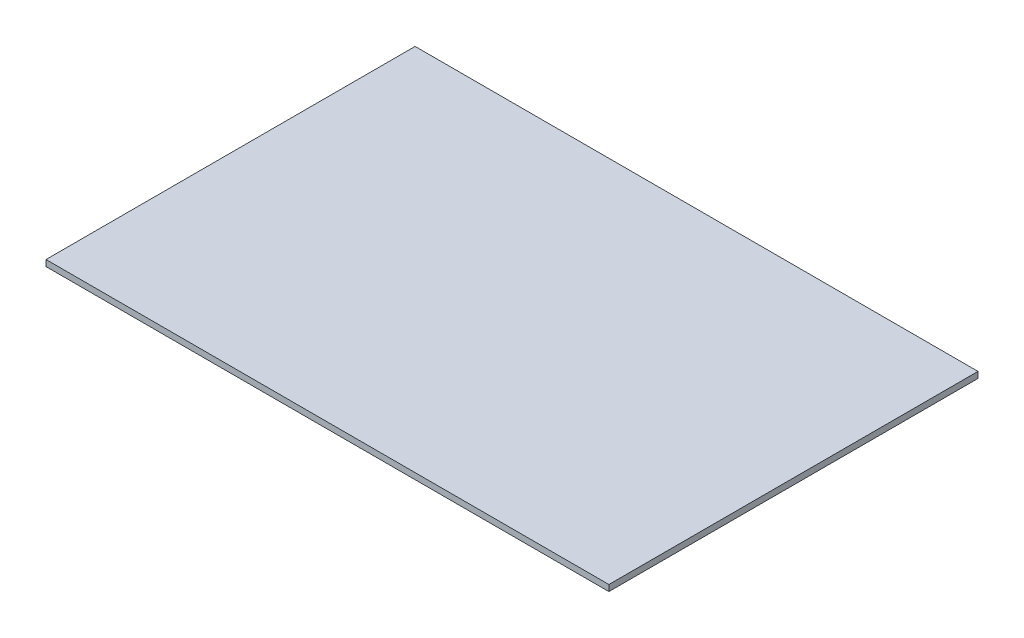
SolidWorks part; units mm, degrees
ref_plane "Front Plane" through (0, 0, 0) normal (0, 0, 1) x (1, 0, 0)
ref_plane "Top Plane" through (0, 0, 0) normal (0, 1, 0) x (1, 0, 0)
ref_plane "Right Plane" through (0, 0, 0) normal (1, 0, 0) x (0, 0, -1)
sketch "Sketch1" plane through (0, 0, 0) normal (0, 1, 0) x (1, 0, 0)
  line L1 (0, 0) -> (914.4, 0)
  line L2 (0, 0) -> (0, 609.6)
  line L3 (0, 609.6) -> (914.4, 609.6)
  line L4 (914.4, 0) -> (914.4, 609.6)
  dimension "D1" = 914.4
  dimension "D2" = 609.6
extrude "Boss-Extrude1" add sketch "Sketch1" along normal blind 5.8
sketch "Sketch2" plane through (0, 5.8, 0) normal (0, 1, 0) x (1, 0, 0)
  line L0 (0, 609.6) -> (70, 609.6) construction
  line L1 (70, 609.6) -> (70, 409.6) construction
  line L2 (70, 409.6) -> (70, 329.6) construction
  line L3 (70, 329.6) -> (70, 249.6) construction
  line L4 (70, 249.6) -> (70, 169.6) construction
  line L5 (70, 169.6) -> (70, 89.6) construction
  line L6 (70, 409.6) -> (170, 409.6) construction
  line L7 (70, 329.6) -> (170, 329.6) construction
  line L8 (70, 249.6) -> (170, 249.6) construction
  line L9 (70, 169.6) -> (170, 169.6) construction
  line L10 (70, 89.6) -> (170, 89.6) construction
  line L11 (170, 409.6) -> (170, 434.6) construction
  line L12 (120, 409.6) -> (120, 434.6) construction
  line L13 (70, 369.6) -> (117.6759, 369.6)
  line L14 (120, 329.6) -> (120, 304.6) construction
  line L15 (170, 329.6) -> (170, 304.6) construction
  line L16 (70, 289.6) -> (96.5119, 289.6)
  line L17 (170, 249.6) -> (170, 274.6) construction
  line L18 (120, 249.6) -> (120, 274.6) construction
  line L19 (70, 209.6) -> (87.6759, 209.6)
  line L20 (70, 129.6) -> (91.522, 129.6)
  circle A0 centre (70, 409.6) radius 11
  circle A1 centre (70, 329.6) radius 11
  circle A2 centre (70, 249.6) radius 11
  circle A3 centre (70, 169.6) radius 11
  circle A4 centre (70, 89.6) radius 11
  circle A5 centre (170, 409.6) radius 4
  circle A6 centre (120, 409.6) radius 4
  circle A7 centre (120, 434.6) radius 4
  circle A8 centre (170, 434.6) radius 4
  circle A9 centre (170, 384.6) radius 4
  circle A10 centre (120, 384.6) radius 4
  circle A11 centre (120, 354.6) radius 4
  circle A12 centre (170, 354.6) radius 4
  circle A13 centre (170, 304.6) radius 4
  circle A14 centre (120, 304.6) radius 4
  circle A15 centre (120, 329.6) radius 4
  circle A16 centre (170, 329.6) radius 4
  circle A17 centre (170, 249.6) radius 4
  circle A18 centre (120, 249.6) radius 4
  circle A19 centre (120, 274.6) radius 4
  circle A20 centre (170, 274.6) radius 4
  circle A21 centre (170, 224.6) radius 4
  circle A22 centre (120, 224.6) radius 4
  circle A23 centre (120, 194.6) radius 4
  circle A24 centre (170, 194.6) radius 4
  circle A25 centre (170, 144.6) radius 4
  circle A26 centre (120, 144.6) radius 4
  circle A27 centre (120, 114.6) radius 4
  circle A28 centre (170, 114.6) radius 4
  circle A29 centre (170, 64.6) radius 4
  circle A30 centre (120, 64.6) radius 4
  dimension "D3" = 22
  dimension "D5" = 22
  dimension "D7" = 8
  dimension "D1" = 70
  dimension "D2" = 200
  dimension "D4" = 80
  dimension "D6" = 100
  dimension "D8" = 25
extrude "Holes For Button, LED, and BananaPins" cut sketch "Sketch2" against normal through all both and the other way through all contours A0 | A6 | A7 | A8 | A5 | A10 | A9 | A12 | A11 | A15 | A16 | A13 | A14 | A19 | A18 | A20 | A17 | A21 | A24 | A23 | A22 | A25 | A26 | A27 | A28 | A29 | A30 | A4 | A3 | A2 | A1 region at (70, 5.8, -409.6) region at (70, 5.8, -329.6) region at (70, 5.8, -249.6) region at (70, 5.8, -169.6) region at (70, 5.8, -89.6) region at (170, 5.8, -409.6) region at (120, 5.8, -409.6) region at (120, 5.8, -434.6) region at (170, 5.8, -434.6) region at (170, 5.8, -384.6) region at (120, 5.8, -384.6) region at (120, 5.8, -354.6) region at (170, 5.8, -354.6) region at (170, 5.8, -304.6) region at (120, 5.8, -304.6) region at (120, 5.8, -329.6) region at (170, 5.8, -329.6) region at (170, 5.8, -249.6) region at (120, 5.8, -249.6) region at (120, 5.8, -274.6) region at (170, 5.8, -274.6) region at (170, 5.8, -224.6) region at (120, 5.8, -224.6) region at (120, 5.8, -194.6) region at (170, 5.8, -194.6) region at (170, 5.8, -144.6) region at (120, 5.8, -144.6) region at (120, 5.8, -114.6) region at (170, 5.8, -114.6) region at (170, 5.8, -64.6) region at (120, 5.8, -64.6)
sketch "Sketch4" plane through (0, 5.8, 0) normal (0, 1, 0) x (1, 0, 0)
  line L0 (70, 409.6) -> (220, 409.6) construction
  line L1 (220, 409.6) -> (220, 459.6) construction
  line L2 (220, 459.6) -> (240, 459.6) construction
  line L3 (240, 459.6) -> (240, 439.6) construction
  line L4 (240, 459.6) -> (240, 479.6) construction
  line L5 (240, 459.6) -> (280, 459.6)
  line L6 (280, 459.6) -> (280, 479.6) construction
  line L7 (280, 459.6) -> (280, 439.6) construction
  line L8 (240, 379.6) -> (280, 379.6)
  line L9 (240, 379.6) -> (240, 359.6) construction
  line L10 (240, 379.6) -> (240, 399.6) construction
  line L11 (280, 379.6) -> (280, 399.6) construction
  line L12 (280, 379.6) -> (280, 359.6) construction
  line L13 (240, 299.6) -> (280, 299.6)
  line L14 (240, 299.6) -> (240, 279.6) construction
  line L15 (240, 299.6) -> (240, 319.6) construction
  line L16 (280, 299.6) -> (280, 319.6) construction
  line L17 (280, 299.6) -> (280, 279.6) construction
  line L18 (240, 219.6) -> (280, 219.6)
  line L19 (240, 219.6) -> (240, 199.6) construction
  line L20 (240, 219.6) -> (240, 239.6) construction
  line L21 (280, 219.6) -> (280, 239.6) construction
  line L22 (280, 219.6) -> (280, 199.6) construction
  line L23 (240, 139.6) -> (280, 139.6)
  line L24 (240, 139.6) -> (240, 119.6) construction
  line L25 (240, 139.6) -> (240, 159.6) construction
  line L26 (280, 139.6) -> (280, 159.6) construction
  line L27 (280, 139.6) -> (280, 119.6) construction
  line L28 (240, 59.6) -> (280, 59.6)
  line L29 (240, 59.6) -> (240, 39.6) construction
  line L30 (240, 59.6) -> (240, 79.6) construction
  line L31 (280, 59.6) -> (280, 79.6) construction
  line L32 (280, 59.6) -> (280, 39.6) construction
  circle A0 centre (240, 479.6) radius 4
  circle A1 centre (240, 439.6) radius 4
  circle A2 centre (280, 479.6) radius 4
  circle A3 centre (280, 459.6) radius 4
  circle A4 centre (280, 439.6) radius 4
  circle A5 centre (310, 479.6) radius 4
  circle A6 centre (310, 459.6) radius 4
  circle A7 centre (310, 439.6) radius 4
  circle A8 centre (340, 479.6) radius 4
  circle A9 centre (340, 459.6) radius 4
  circle A10 centre (340, 439.6) radius 4
  circle A11 centre (370, 479.6) radius 4
  circle A12 centre (370, 459.6) radius 4
  circle A13 centre (370, 439.6) radius 4
  circle A14 centre (400, 479.6) radius 4
  circle A15 centre (400, 459.6) radius 4
  circle A16 centre (400, 439.6) radius 4
  circle A17 centre (430, 479.6) radius 4
  circle A18 centre (430, 459.6) radius 4
  circle A19 centre (430, 439.6) radius 4
  circle A20 centre (240, 399.6) radius 4
  circle A21 centre (240, 359.6) radius 4
  circle A22 centre (280, 399.6) radius 4
  circle A23 centre (280, 379.6) radius 4
  circle A24 centre (280, 359.6) radius 4
  circle A25 centre (310, 399.6) radius 4
  circle A26 centre (310, 379.6) radius 4
  circle A27 centre (310, 359.6) radius 4
  circle A28 centre (340, 399.6) radius 4
  circle A29 centre (340, 379.6) radius 4
  circle A30 centre (340, 359.6) radius 4
  circle A31 centre (370, 399.6) radius 4
  circle A32 centre (370, 379.6) radius 4
  circle A33 centre (370, 359.6) radius 4
  circle A34 centre (400, 399.6) radius 4
  circle A35 centre (400, 379.6) radius 4
  circle A36 centre (400, 359.6) radius 4
  circle A37 centre (430, 399.6) radius 4
  circle A38 centre (430, 379.6) radius 4
  circle A39 centre (430, 359.6) radius 4
  circle A40 centre (240, 319.6) radius 4
  circle A41 centre (240, 279.6) radius 4
  circle A42 centre (280, 319.6) radius 4
  circle A43 centre (280, 299.6) radius 4
  circle A44 centre (280, 279.6) radius 4
  circle A45 centre (310, 319.6) radius 4
  circle A46 centre (310, 299.6) radius 4
  circle A47 centre (310, 279.6) radius 4
  circle A48 centre (340, 319.6) radius 4
  circle A49 centre (340, 299.6) radius 4
  circle A50 centre (340, 279.6) radius 4
  circle A51 centre (370, 319.6) radius 4
  circle A52 centre (370, 299.6) radius 4
  circle A53 centre (370, 279.6) radius 4
  circle A54 centre (400, 319.6) radius 4
  circle A55 centre (400, 299.6) radius 4
  circle A56 centre (400, 279.6) radius 4
  circle A57 centre (430, 319.6) radius 4
  circle A58 centre (430, 299.6) radius 4
  circle A59 centre (430, 279.6) radius 4
  circle A60 centre (240, 239.6) radius 4
  circle A61 centre (240, 199.6) radius 4
  circle A62 centre (280, 239.6) radius 4
  circle A63 centre (280, 219.6) radius 4
  circle A64 centre (280, 199.6) radius 4
  circle A65 centre (310, 239.6) radius 4
  circle A66 centre (310, 219.6) radius 4
  circle A67 centre (310, 199.6) radius 4
  circle A68 centre (340, 239.6) radius 4
  circle A69 centre (340, 219.6) radius 4
  circle A70 centre (340, 199.6) radius 4
  circle A71 centre (370, 239.6) radius 4
  circle A72 centre (370, 219.6) radius 4
  circle A73 centre (370, 199.6) radius 4
  circle A74 centre (400, 239.6) radius 4
  circle A75 centre (400, 219.6) radius 4
  circle A76 centre (400, 199.6) radius 4
  circle A77 centre (430, 239.6) radius 4
  circle A78 centre (430, 219.6) radius 4
  circle A79 centre (430, 199.6) radius 4
  circle A80 centre (240, 159.6) radius 4
  circle A81 centre (240, 119.6) radius 4
  circle A82 centre (280, 159.6) radius 4
  circle A83 centre (280, 139.6) radius 4
  circle A84 centre (280, 119.6) radius 4
  circle A85 centre (310, 159.6) radius 4
  circle A86 centre (310, 139.6) radius 4
  circle A87 centre (310, 119.6) radius 4
  circle A88 centre (340, 159.6) radius 4
  circle A89 centre (340, 139.6) radius 4
  circle A90 centre (340, 119.6) radius 4
  circle A91 centre (370, 159.6) radius 4
  circle A92 centre (370, 139.6) radius 4
  circle A93 centre (370, 119.6) radius 4
  circle A94 centre (400, 159.6) radius 4
  circle A95 centre (400, 139.6) radius 4
  circle A96 centre (400, 119.6) radius 4
  circle A97 centre (430, 159.6) radius 4
  circle A98 centre (430, 139.6) radius 4
  circle A99 centre (430, 119.6) radius 4
  circle A100 centre (240, 79.6) radius 4
  circle A101 centre (240, 39.6) radius 4
  circle A102 centre (280, 79.6) radius 4
  circle A103 centre (280, 59.6) radius 4
  circle A104 centre (280, 39.6) radius 4
  circle A105 centre (310, 79.6) radius 4
  circle A106 centre (310, 59.6) radius 4
  circle A107 centre (310, 39.6) radius 4
  circle A108 centre (340, 79.6) radius 4
  circle A109 centre (340, 59.6) radius 4
  circle A110 centre (340, 39.6) radius 4
  circle A111 centre (370, 79.6) radius 4
  circle A112 centre (370, 59.6) radius 4
  circle A113 centre (370, 39.6) radius 4
  circle A114 centre (400, 79.6) radius 4
  circle A115 centre (400, 59.6) radius 4
  circle A116 centre (400, 39.6) radius 4
  circle A117 centre (430, 79.6) radius 4
  circle A118 centre (430, 59.6) radius 4
  circle A119 centre (430, 39.6) radius 4
  dimension "D6" = 8
  dimension "D1" = 150
  dimension "D2" = 50
  dimension "D3" = 20
  dimension "D4" = 20
  dimension "D5" = 40
  dimension "D7" = 6
  dimension "D8" = 6
extrude "Cut-Extrude2" cut sketch "Sketch4" against normal through all both contours A119 | A116 | A113 | A110 | A107 | A104 | A101 | A103 | A105 | A108 | A114 | A117 | A97 | A99 | A98 | A95 | A94 | A96 | A93 | A90 | A87 | A86 | A85 | A82 | A83 | A84 | A80 | A79 | A78 | A77 | A74 | A75 | A76 | A73 | A72 | A71 | A69 | A67 | A66 | A65 | A63 | A64 | A61 | A60 | A44 | A41 | A40 | A45 | A47 | A50 | A48 | A51 | A52 | A49 | A46 | A55 | A56 | A54 | A57 | A20 | A21 | A24 | A23 | A22 | A25 | A26 | A30 | A29 | A28 | A33 | A35 | A34 | A38 | A39 | A19 | A18 | A17 | A14 | A15 | A16 | A13 | A12 | A11 | A8 | A9 | A10 | A6 | A5 | A118 | A115 | A112 | A109 | A106 | A102 | A100 | A111 | A92 | A91 | A88 | A81 | A68 | A70 | A62 | A43 | A42 | A53 | A58 | A59 | A27 | A32 | A36 | A31 | A37 | A7 | A4 | A3 | A2 | A0 | A1 | A89 region at (310, 5.8, -479.6) region at (310, 5.8, -459.6) region at (340, 5.8, -479.6) region at (340, 5.8, -459.6) region at (340, 5.8, -439.6) region at (370, 5.8, -479.6) region at (370, 5.8, -459.6) region at (370, 5.8, -439.6) region at (400, 5.8, -479.6) region at (400, 5.8, -459.6) region at (400, 5.8, -439.6) region at (430, 5.8, -479.6) region at (430, 5.8, -459.6) region at (430, 5.8, -439.6) region at (240, 5.8, -399.6) region at (240, 5.8, -359.6) region at (280, 5.8, -399.6) region at (280, 5.8, -375.7131) region at (280, 5.8, -359.6) region at (310, 5.8, -399.6) region at (310, 5.8, -379.6) region at (340, 5.8, -399.6) region at (340, 5.8, -379.6) region at (340, 5.8, -359.6) region at (370, 5.8, -359.6) region at (400, 5.8, -399.6) region at (400, 5.8, -379.6) region at (430, 5.8, -379.6) region at (430, 5.8, -359.6) region at (240, 5.8, -319.6) region at (240, 5.8, -279.6) region at (280, 5.8, -279.6) region at (310, 5.8, -319.6) region at (310, 5.8, -299.6) region at (310, 5.8, -279.6) region at (340, 5.8, -319.6) region at (340, 5.8, -299.6) region at (340, 5.8, -279.6) region at (370, 5.8, -319.6) region at (370, 5.8, -299.6) region at (400, 5.8, -319.6) region at (400, 5.8, -299.6) region at (400, 5.8, -279.6) region at (430, 5.8, -319.6) region at (240, 5.8, -239.6) region at (240, 5.8, -199.6) region at (280, 5.8, -215.7131) region at (280, 5.8, -199.6) region at (310, 5.8, -239.6) region at (310, 5.8, -219.6) region at (310, 5.8, -199.6) region at (340, 5.8, -219.6) region at (370, 5.8, -239.6) region at (370, 5.8, -219.6) region at (370, 5.8, -199.6) region at (400, 5.8, -239.6) region at (400, 5.8, -219.6) region at (400, 5.8, -199.6) region at (430, 5.8, -239.6) region at (430, 5.8, -219.6)
sketch "Sketch6" plane through (0, 0, -609.6) normal (0, 0, -1) x (-1, 0, 0)
  line L4 (-914.4, 0) -> (0, 0)
  line L5 (0, 0) -> (0, 5.8)
  line L6 (0, 5.8) -> (-914.4, 5.8)
  line L7 (-914.4, 5.8) -> (-914.4, 0)
  line L8 (-914.4, 0) -> (0, 0)
  line L9 (0, 0) -> (0, 5.8)
  line L10 (0, 5.8) -> (-914.4, 5.8)
  line L11 (-914.4, 5.8) -> (-914.4, 0)
  dimension "D1" = 0
extrude "Cut-Extrude3" cut sketch "Sketch6" against normal blind 20
sketch "Sketch7" plane through (0, 0, 0) normal (0, 0, 1) x (1, 0, 0)
  line L4 (0, 0) -> (914.4, 0)
  line L5 (914.4, 0) -> (914.4, 5.8)
  line L6 (914.4, 5.8) -> (0, 5.8)
  line L7 (0, 5.8) -> (0, 0)
  line L8 (0, 0) -> (914.4, 0)
  line L9 (914.4, 0) -> (914.4, 5.8)
  line L10 (914.4, 5.8) -> (0, 5.8)
  line L11 (0, 5.8) -> (0, 0)
  dimension "D1" = 0
extrude "Boss-Extrude3" add sketch "Sketch7" along normal blind 10
sketch "Sketch8" plane through (0, 0, -589.6) normal (0, 0, -1) x (-1, 0, 0)
  line L4 (-914.4, 5.8) -> (-914.4, 0)
  line L5 (-914.4, 0) -> (0, 0)
  line L6 (0, 0) -> (0, 5.8)
  line L7 (0, 5.8) -> (-914.4, 5.8)
  line L8 (-914.4, 5.8) -> (-914.4, 0)
  line L9 (-914.4, 0) -> (0, 0)
  line L10 (0, 0) -> (0, 5.8)
  line L11 (0, 5.8) -> (-914.4, 5.8)
  dimension "D1" = 0
extrude "Boss-Extrude4" add sketch "Sketch8" along normal blind 10
sketch "Sketch9" plane through (0, 5.8, 0) normal (0, 1, 0) x (1, 0, 0)
  line L0 (95, 14.6) -> (470, 14.6) construction
  line L5 (470, 14.6) -> (470, 99.6) construction
  line L8 (426, 479.6) -> (426, 39.6) construction
  line L9 (426, 259.6) -> (349.7894, 259.6) construction
  circle A0 centre (95, 14.6) radius 4
  circle A1 centre (470, 99.6) radius 4
  circle A2 centre (470, 14.6) radius 4
  circle A3 centre (205, 14.6) radius 4
  circle A4 centre (260, 14.6) radius 4
  circle A5 centre (430, 479.6) radius 4 construction
  circle A6 centre (430, 39.6) radius 4 construction
  circle A7 centre (95, 504.6) radius 4
  circle A8 centre (205, 504.6) radius 4
  circle A9 centre (260, 504.6) radius 4
  circle A10 centre (470, 504.6) radius 4
  circle A11 centre (470, 419.6) radius 4
extrude "Cut-Extrude4" cut sketch "Sketch9" against normal blind 10
sketch "Sketch10" plane through (0, 0, 10) normal (0, 0, 1) x (1, 0, 0)
  line L4 (0, 5.8) -> (0, 0)
  line L5 (0, 0) -> (914.4, 0)
  line L6 (914.4, 0) -> (914.4, 5.8)
  line L7 (914.4, 5.8) -> (0, 5.8)
  line L8 (0, 5.8) -> (0, 0)
  line L9 (0, 0) -> (914.4, 0)
  line L10 (914.4, 0) -> (914.4, 5.8)
  line L11 (914.4, 5.8) -> (0, 5.8)
  dimension "D1" = 0
extrude "Boss-Extrude5" add sketch "Sketch10" along normal blind 10
sketch "Sketch11" plane through (0, 0, -599.6) normal (0, 0, -1) x (-1, 0, 0)
  line L4 (0, 5.8) -> (-914.4, 5.8)
  line L5 (-914.4, 5.8) -> (-914.4, 0)
  line L6 (-914.4, 0) -> (0, 0)
  line L7 (0, 0) -> (0, 5.8)
  line L8 (0, 5.8) -> (-914.4, 5.8)
  line L9 (-914.4, 5.8) -> (-914.4, 0)
  line L10 (-914.4, 0) -> (0, 0)
  line L11 (0, 0) -> (0, 5.8)
  dimension "D1" = 0
extrude "Cut-Extrude5" cut sketch "Sketch11" against normal blind 10
sketch "Sketch12" plane through (0, 5.8, 0) normal (0, 1, 0) x (1, 0, 0)
  line L0 (844.4, 589.6) -> (844.4, -20) construction
  line L1 (0, 589.6) -> (914.4, 589.6) construction
  line L2 (914.4, -20) -> (0, -20) construction
  line L3 (914.4, -20) -> (914.4, 589.6) construction
  line L4 (679.4, 289.2973) -> (694.2018, 289.2973) construction
  line L5 (514.4, 382.1) -> (844.4, 382.1) construction
  line L6 (514.4, 504.6) -> (844.4, 504.6) construction
  line L7 (514.4, 14.6) -> (844.4, 14.6) construction
  line L8 (679.4, 259.6) -> (514.4, 259.6) construction
  line L9 (514.4, 259.6) -> (514.4, 504.6) construction
  line L10 (624.4, 279.6) -> (624.4, 284.6) construction
  line L11 (596.9, 443.35) -> (514.4, 443.35) construction
  line L12 (514.4, 279.6) -> (734.4, 279.6) construction
  line L13 (624.4, 284.6) -> (632.4, 284.6) construction
  line L14 (624.4, 279.6) -> (624.4, 354.6) construction
  line L15 (624.4, 317.1) -> (709.4, 317.1) construction
  line L16 (709.4, 317.1) -> (739.4, 317.1) construction
  line L17 (679.4, 317.1) -> (679.4, 259.6) construction
  line L18 (679.4, 504.6) -> (679.4, 14.6) construction
  line L19 (514.4, 137.1) -> (844.4, 137.1) construction
  line L20 (514.4, 279.6) -> (514.4, 14.6) construction
  line L21 (514.4, 145.6564) -> (555.9031, 145.6564) construction
  line L22 (624.4, 504.6) -> (624.4, 284.6)
  line L23 (624.4, 284.6) -> (624.4, 64.6)
  line L24 (624.4, 174.6) -> (673.01, 174.6)
  circle A0 centre (634.65, 284.6) radius 2.25
  circle A1 centre (614.15, 284.6) radius 2.25
  circle A2 centre (739.4, 317.1) radius 4
  circle A3 centre (509.4, 317.1) radius 4
  circle A4 centre (509.4, 261.4945) radius 4
  circle A5 centre (739.4, 261.4945) radius 4
  circle A6 centre (614.15, 64.6) radius 2.25
  circle A7 centre (634.65, 64.6) radius 2.25
  circle A8 centre (509.4, 87.7055) radius 4
  circle A9 centre (509.4, 32.1) radius 4
  circle A10 centre (739.4, 87.7055) radius 4
  circle A11 centre (739.4, 32.1) radius 4
  dimension "D2" = 8
  dimension "D1" = 70
  dimension "D3" = 220
  dimension "D4" = 220
extrude "Cut-Extrude6" cut sketch "Sketch12" against normal blind 10 contours A2 | A5 | A0 | A1 | A3 | A4 | A7 | A6 | A9 | A8 | A11 | A10 region at (634.65, 5.8, -284.6) region at (614.15, 5.8, -284.6) region at (739.4, 5.8, -317.1) region at (509.4, 5.8, -317.1) region at (509.4, 5.8, -261.4945) region at (739.4, 5.8, -261.4945) region at (614.15, 5.8, -64.6) region at (634.65, 5.8, -64.6) region at (509.4, 5.8, -87.7055) region at (509.4, 5.8, -32.1) region at (739.4, 5.8, -87.7055) region at (739.4, 5.8, -32.1)
sketch "Sketch13" plane through (0, 5.8, 0) normal (0, 1, 0) x (1, 0, 0)
  line L0 (614.15, 64.6) -> (634.65, 64.6)
  line L1 (624.4, 64.6) -> (624.4, 164.6)
  line L2 (624.4, 164.6) -> (624.4, 204.6)
  line L3 (470, 508.6) -> (870, 508.6) construction
  line L4 (870, 508.6) -> (870, 10.6) construction
  line L5 (470, 10.6) -> (870, 10.6) construction
  line L6 (614.15, 284.6) -> (614.15, 294.6) construction
  line L7 (614.15, 294.6) -> (634.65, 294.6) construction
  circle A0 centre (470, 504.6) radius 4 construction
  circle A1 centre (470, 14.6) radius 4 construction
  circle A14 centre (509.4, 272.1) radius 4
  circle A15 centre (509.4, 327.7055) radius 4
  circle A16 centre (739.4, 327.7055) radius 4
  circle A17 centre (739.4, 272.1) radius 4
  circle A18 centre (634.65, 304.6) radius 2.25
  circle A19 centre (614.15, 304.6) radius 2.25
  dimension "D1" = 100
  dimension "D2" = 40
  dimension "D3" = 400
  dimension "D4" = 10
extrude "Cut-Extrude7" cut sketch "Sketch13" against normal blind 10 contours A17 | A16 | A18 | A19 | A15 | A14 region at (509.4, 5.8, -272.1) region at (509.4, 5.8, -327.7055) region at (739.4, 5.8, -327.7055) region at (739.4, 5.8, -272.1) region at (634.65, 5.8, -304.6) region at (614.15, 5.8, -304.6)
sketch "Sketch14" plane through (0, 5.8, 0) normal (0, 1, 0) x (1, 0, 0)
  circle A0 centre (739.4, 317.1) radius 4 construction
  circle A1 centre (739.4, 261.4945) radius 4 construction
  circle A2 centre (634.65, 284.6) radius 2.25 construction
  circle A3 centre (614.15, 284.6) radius 2.25 construction
  circle A4 centre (509.4, 261.4945) radius 4 construction
  circle A5 centre (509.4, 317.1) radius 4 construction
  circle A6 centre (739.4, 317.1) radius 4
  circle A7 centre (739.4, 261.4945) radius 4
  circle A8 centre (634.65, 284.6) radius 2.25
  circle A9 centre (614.15, 284.6) radius 2.25
  circle A10 centre (509.4, 261.4945) radius 4
  circle A11 centre (509.4, 317.1) radius 4
extrude "Boss-Extrude6" add sketch "Sketch14" against normal up to surface (5.8 mm away) up to face at (509.4, 0, -276.1)
sketch "Sketch15" plane through (0, 5.8, 0) normal (0, 1, 0) x (1, 0, 0)
  line L0 (614.15, 304.6) -> (614.15, 384.6) construction
  line L1 (614.15, 384.6) -> (524.15, 384.6)
  line L2 (524.15, 384.6) -> (524.15, 425.13)
  line L3 (524.15, 425.13) -> (731.75, 425.13)
  line L4 (731.75, 425.13) -> (731.75, 384.6)
  line L5 (731.75, 384.6) -> (614.15, 384.6)
  line L6 (731.75, 404.865) -> (666.9, 404.865)
  line L7 (666.9, 404.865) -> (569, 404.865)
  line L8 (524.15, 404.865) -> (859.15, 404.865)
  line L9 (859.15, 404.865) -> (859.15, 415.865)
  line L10 (859.15, 415.865) -> (731.75, 415.865)
  line L11 (859.15, 415.865) -> (859.15, 450.865)
  line L12 (859.15, 450.865) -> (709.15, 450.865)
  line L13 (859.15, 450.865) -> (879.15, 450.865)
  line L14 (709.15, 450.865) -> (879.15, 450.865) construction
  line L15 (709.15, 453.365) -> (879.15, 453.365)
  line L16 (709.15, 448.365) -> (879.15, 448.365)
  line L17 (614.15, 64.6) -> (614.15, 144.6)
  line L18 (614.15, 384.6) -> (614.15, 144.6)
  line L19 (614.15, 264.6) -> (569, 264.6)
  line L20 (614.15, 144.6) -> (524.15, 144.6)
  line L21 (524.15, 144.6) -> (524.15, 185.13)
  line L22 (524.15, 185.13) -> (731.75, 185.13)
  line L23 (731.75, 185.13) -> (731.75, 144.6)
  line L24 (731.75, 144.6) -> (614.15, 144.6)
  line L25 (731.75, 164.865) -> (666.9, 164.865)
  line L26 (666.9, 164.865) -> (569, 164.865)
  line L27 (859.15, 210.865) -> (709.15, 210.865)
  line L28 (859.15, 210.865) -> (879.15, 210.865)
  line L29 (709.15, 210.865) -> (879.15, 210.865) construction
  line L30 (709.15, 213.365) -> (879.15, 213.365)
  line L31 (709.15, 208.365) -> (879.15, 208.365)
  circle A0 centre (666.9, 404.865) radius 2.5
  circle A1 centre (569, 404.865) radius 2.5
  arc A2 (709.15, 453.365) -> (709.15, 448.365) centre (709.15, 450.865) ccw
  arc A3 (879.15, 448.365) -> (879.15, 453.365) centre (879.15, 450.865) ccw
  circle A4 centre (666.9, 164.865) radius 2.5
  circle A5 centre (569, 164.865) radius 2.5
  arc A6 (709.15, 213.365) -> (709.15, 208.365) centre (709.15, 210.865) ccw
  arc A7 (879.15, 208.365) -> (879.15, 213.365) centre (879.15, 210.865) ccw
  point P14 (794.15, 450.865)
  point P41 (794.15, 210.865)
  dimension "D6" = 5
  dimension "D8" = 5
  dimension "D1" = 80
  dimension "D2" = 90
  dimension "D3" = 40.53
  dimension "D4" = 207.6
  dimension "D5" = 64.85
  dimension "D7" = 97.9
  dimension "D9" = 335
  dimension "D10" = 11
  dimension "D11" = 35
  dimension "D12" = 150
  dimension "D13" = 20
  dimension "D14" = 5
  dimension "D15" = 80
  dimension "D16" = 2
extrude "Cut-Extrude8" cut sketch "Sketch15" against normal through all both and the other way through all contours L26 A4 L25 | L25 A4 L26 | A5 | L31 A7 L30 A6 | L7 A0 L8 | L8 A0 L7 | L8 A1 L7 | L7 A1 L8 | L16 A3 L15 A2 region at (784.15, 5.8, -450.1157) region at (566.5707, 5.8, -164.865) region at (569, 5.8, -405.926) region at (569, 5.8, -403.804) region at (666.9, 5.8, -403.804) region at (666.9, 5.8, -405.926) region at (666.9, 5.8, -165.926) region at (666.9, 5.8, -163.804) region at (794.15, 5.8, -211.6143)
sketch "Sketch16" plane through (0, 5.8, 0) normal (0, 1, 0) x (1, 0, 0)
  line L0 (794.15, 453.365) -> (794.15, 483.365)
  line L1 (709.15, 453.365) -> (879.15, 453.365) construction
  line L2 (794.15, 483.365) -> (764.15, 483.365)
  line L3 (794.15, 483.365) -> (824.15, 483.365)
  line L4 (794.15, 483.365) -> (794.15, 213.365)
  line L5 (709.15, 213.365) -> (879.15, 213.365) construction
  circle A0 centre (824.15, 483.365) radius 4
  circle A1 centre (844.15, 483.365) radius 4
  circle A2 centre (864.15, 483.365) radius 4
  circle A3 centre (764.15, 483.365) radius 4
  circle A4 centre (744.15, 483.365) radius 4
  circle A5 centre (724.15, 483.365) radius 4
  circle A6 centre (764.15, 243.365) radius 4
  circle A7 centre (744.15, 243.365) radius 4
  circle A8 centre (724.15, 243.365) radius 4
  circle A9 centre (824.15, 243.365) radius 4
  circle A10 centre (844.15, 243.365) radius 4
  circle A11 centre (864.15, 243.365) radius 4
  dimension "D3" = 8
  dimension "D5" = 8
  dimension "D1" = 30
  dimension "D2" = 30
  dimension "D4" = 3
  dimension "D6" = 3
  dimension "D7" = 2
extrude "Cut-Extrude9" cut sketch "Sketch16" against normal through all both contours A11 | A10 | A9 | A6 | A7 | A8 | A2 | A1 | A0 | A3 | A4 | A5 region at (760.2631, 5.8, -483.365) region at (824.15, 5.8, -487.2519) region at (844.15, 5.8, -483.365) region at (864.15, 5.8, -483.365) region at (744.15, 5.8, -483.365) region at (724.15, 5.8, -483.365) region at (764.15, 5.8, -243.365) region at (744.15, 5.8, -243.365) region at (724.15, 5.8, -243.365) region at (824.15, 5.8, -243.365) region at (844.15, 5.8, -243.365) region at (864.15, 5.8, -243.365)
sketch "Sketch17" plane through (0, 5.8, 0) normal (0, 1, 0) x (1, 0, 0)
  line L0 (614.15, 304.6) -> (634.65, 304.6)
  line L1 (624.4, 304.6) -> (624.4, 349.6)
  line L2 (614.15, 64.6) -> (634.65, 64.6)
  line L3 (624.4, 64.6) -> (624.4, 109.6)
  circle A0 centre (624.4, 349.6) radius 2.5
  circle A1 centre (624.4, 109.6) radius 2.5
  dimension "D2" = 5
  dimension "D4" = 5
  dimension "D1" = 45
  dimension "D3" = 45
extrude "Cut-Extrude10" cut sketch "Sketch17" against normal through all both contours A1 | A0 region at (626.1178, 5.8, -347.8822) region at (626.1178, 5.8, -107.8822)
sketch "Sketch19" plane through (0, 0, 0) normal (-1, 0, 0) x (0, 0, 1)
  line L4 (-589.6, 5.8) -> (-589.6, 0)
  line L5 (-589.6, 0) -> (20, 0)
  line L6 (20, 0) -> (20, 5.8)
  line L7 (20, 5.8) -> (-589.6, 5.8)
  line L8 (-589.6, 5.8) -> (-589.6, 0)
  line L9 (-589.6, 0) -> (20, 0)
  line L10 (20, 0) -> (20, 5.8)
  line L11 (20, 5.8) -> (-589.6, 5.8)
  dimension "D1" = 0
extrude "Cut-Extrude11" cut sketch "Sketch19" against normal blind 20
sketch "Sketch20" plane through (914.4, 0, 0) normal (1, 0, 0) x (0, 0, -1)
  line L4 (589.6, 0) -> (589.6, 5.8)
  line L5 (589.6, 5.8) -> (-20, 5.8)
  line L6 (-20, 5.8) -> (-20, 0)
  line L7 (-20, 0) -> (589.6, 0)
  line L8 (589.6, 0) -> (589.6, 5.8)
  line L9 (589.6, 5.8) -> (-20, 5.8)
  line L10 (-20, 5.8) -> (-20, 0)
  line L11 (-20, 0) -> (589.6, 0)
  dimension "D1" = 0
extrude "Boss-Extrude7" add sketch "Sketch20" along normal blind 20
sketch "Sketch22" plane through (934.4, 0, 0) normal (1, 0, 0) x (0, 0, -1)
  line L4 (-20, 0) -> (589.6, 0)
  line L5 (589.6, 0) -> (589.6, 5.8)
  line L6 (589.6, 5.8) -> (-20, 5.8)
  line L7 (-20, 5.8) -> (-20, 0)
  line L8 (-20, 0) -> (589.6, 0)
  line L9 (589.6, 0) -> (589.6, 5.8)
  line L10 (589.6, 5.8) -> (-20, 5.8)
  line L11 (-20, 5.8) -> (-20, 0)
  dimension "D1" = 0
extrude "Cut-Extrude12" cut sketch "Sketch22" against normal blind 10
sketch "Sketch23" plane through (20, 0, 0) normal (-1, 0, 0) x (0, 0, 1)
  line L4 (20, 5.8) -> (-589.6, 5.8)
  line L5 (-589.6, 5.8) -> (-589.6, 0)
  line L6 (-589.6, 0) -> (20, 0)
  line L7 (20, 0) -> (20, 5.8)
  line L8 (20, 5.8) -> (-589.6, 5.8)
  line L9 (-589.6, 5.8) -> (-589.6, 0)
  line L10 (-589.6, 0) -> (20, 0)
  line L11 (20, 0) -> (20, 5.8)
  dimension "D1" = 0
extrude "Boss-Extrude8" add sketch "Sketch23" along normal blind 10
sketch "Sketch24" plane through (0, 0, 20) normal (0, 0, 1) x (1, 0, 0)
  line L4 (10, 0) -> (924.4, 0)
  line L5 (924.4, 0) -> (924.4, 5.8)
  line L6 (924.4, 5.8) -> (10, 5.8)
  line L7 (10, 5.8) -> (10, 0)
  line L8 (10, 0) -> (924.4, 0)
  line L9 (924.4, 0) -> (924.4, 5.8)
  line L10 (924.4, 5.8) -> (10, 5.8)
  line L11 (10, 5.8) -> (10, 0)
  dimension "D1" = 0
extrude "Boss-Extrude9" add sketch "Sketch24" along normal blind 15
sketch "Sketch25" plane through (0, 0, -589.6) normal (0, 0, -1) x (-1, 0, 0)
  line L4 (-10, 5.8) -> (-924.4, 5.8)
  line L5 (-924.4, 5.8) -> (-924.4, 0)
  line L6 (-924.4, 0) -> (-10, 0)
  line L7 (-10, 0) -> (-10, 5.8)
  line L8 (-10, 5.8) -> (-924.4, 5.8)
  line L9 (-924.4, 5.8) -> (-924.4, 0)
  line L10 (-924.4, 0) -> (-10, 0)
  line L11 (-10, 0) -> (-10, 5.8)
  dimension "D1" = 0
extrude "Cut-Extrude13" cut sketch "Sketch25" against normal blind 15
sketch "Sketch26" plane through (0, 5.8, 0) normal (0, 1, 0) x (1, 0, 0)
  line L0 (569, 404.865) -> (584, 404.865) construction
  line L1 (569, 407.365) -> (584, 407.365)
  line L2 (569, 402.365) -> (584, 402.365)
  line L3 (666.9, 404.865) -> (681.9, 404.865) construction
  line L4 (666.9, 407.365) -> (681.9, 407.365)
  line L5 (666.9, 402.365) -> (681.9, 402.365)
  line L6 (569, 404.865) -> (569, 413.6822)
  line L7 (666.9, 404.865) -> (666.9, 413.6822)
  line L8 (569, 404.865) -> (554, 404.865) construction
  line L9 (569, 407.365) -> (554, 407.365)
  line L10 (569, 402.365) -> (554, 402.365)
  line L11 (666.9, 404.865) -> (651.9, 404.865) construction
  line L12 (666.9, 407.365) -> (651.9, 407.365)
  line L13 (666.9, 402.365) -> (651.9, 402.365)
  line L14 (569, 404.865) -> (569, 164.865)
  line L15 (569, 284.865) -> (556.2872, 284.865)
  line L16 (569, 164.865) -> (584, 164.865) construction
  line L17 (569, 162.365) -> (584, 162.365)
  line L18 (569, 167.365) -> (584, 167.365)
  line L19 (666.9, 164.865) -> (681.9, 164.865) construction
  line L20 (666.9, 162.365) -> (681.9, 162.365)
  line L21 (666.9, 167.365) -> (681.9, 167.365)
  line L22 (569, 164.865) -> (554, 164.865) construction
  line L23 (569, 162.365) -> (554, 162.365)
  line L24 (569, 167.365) -> (554, 167.365)
  line L25 (666.9, 164.865) -> (651.9, 164.865) construction
  line L26 (666.9, 162.365) -> (651.9, 162.365)
  line L27 (666.9, 167.365) -> (651.9, 167.365)
  line L28 (666.9, 164.865) -> (666.9, 156.0478)
  line L29 (569, 164.865) -> (569, 156.0478)
  arc A0 (569, 407.365) -> (569, 402.365) centre (569, 404.865) ccw
  arc A1 (584, 402.365) -> (584, 407.365) centre (584, 404.865) ccw
  arc A2 (666.9, 407.365) -> (666.9, 402.365) centre (666.9, 404.865) ccw
  arc A3 (681.9, 402.365) -> (681.9, 407.365) centre (681.9, 404.865) ccw
  arc A4 (569, 407.365) -> (569, 402.365) centre (569, 404.865) cw
  arc A5 (554, 402.365) -> (554, 407.365) centre (554, 404.865) cw
  arc A6 (666.9, 407.365) -> (666.9, 402.365) centre (666.9, 404.865) cw
  arc A7 (651.9, 402.365) -> (651.9, 407.365) centre (651.9, 404.865) cw
  arc A8 (569, 162.365) -> (569, 167.365) centre (569, 164.865) cw
  arc A9 (584, 167.365) -> (584, 162.365) centre (584, 164.865) cw
  arc A10 (666.9, 162.365) -> (666.9, 167.365) centre (666.9, 164.865) cw
  arc A11 (681.9, 167.365) -> (681.9, 162.365) centre (681.9, 164.865) cw
  arc A12 (569, 162.365) -> (569, 167.365) centre (569, 164.865) ccw
  arc A13 (554, 167.365) -> (554, 162.365) centre (554, 164.865) ccw
  arc A14 (666.9, 162.365) -> (666.9, 167.365) centre (666.9, 164.865) ccw
  arc A15 (651.9, 167.365) -> (651.9, 162.365) centre (651.9, 164.865) ccw
  point P3 (576.5, 404.865)
  point P11 (674.4, 404.865)
  point P21 (561.5, 404.865)
  point P27 (659.4, 404.865)
  point P38 (576.5, 164.865)
  point P45 (674.4, 164.865)
  point P52 (561.5, 164.865)
  point P59 (659.4, 164.865)
  dimension "D1" = 15
  dimension "D2" = 15
  dimension "D3" = 5
  dimension "D4" = 5
extrude "Cut-Extrude14" cut sketch "Sketch26" against normal blind 15 contours A12 L17 A9 L18 | L24 A13 L23 A8 | A14 L20 A11 L21 | L27 A15 L26 A10 | L4 A6 L5 A3 | A7 L13 A2 L12 | L1 A4 L2 A1 | A5 L10 A0 L9 region at (578.4635, 5.8, -164.865) region at (559.5365, 5.8, -164.865) region at (559.5365, 5.8, -404.865) region at (578.4635, 5.8, -404.865) region at (657.4365, 5.8, -404.865) region at (676.3635, 5.8, -404.865) region at (676.3635, 5.8, -164.865) region at (657.4365, 5.8, -164.865)
sketch "Sketch27" plane through (0, 5.8, 0) normal (0, 1, 0) x (1, 0, 0)
  line L0 (614.15, 306.85) -> (634.65, 306.85) construction
  line L1 (624.4, 306.85) -> (624.4, 351.85) construction
  line L2 (624.4, 351.85) -> (655.9, 351.85) construction
  line L3 (614.15, 66.85) -> (634.65, 66.85) construction
  line L4 (624.4, 66.85) -> (624.4, 111.85) construction
  line L5 (624.4, 111.85) -> (655.9, 111.85) construction
  circle A0 centre (634.65, 304.6) radius 2.25 construction
  circle A1 centre (614.15, 304.6) radius 2.25 construction
  circle A2 centre (655.9, 351.85) radius 2.25
  circle A3 centre (592.9, 351.85) radius 2.25
  circle A4 centre (614.15, 64.6) radius 2.25 construction
  circle A5 centre (634.65, 64.6) radius 2.25 construction
  circle A6 centre (655.9, 111.85) radius 2.25
  circle A7 centre (592.9, 111.85) radius 2.25
  dimension "D3" = 4.5
  dimension "D6" = 4.5
  dimension "D1" = 45
  dimension "D2" = 31.5
  dimension "D4" = 45
  dimension "D5" = 31.5
extrude "Cut-Extrude15" cut sketch "Sketch27" against normal blind 10
sketch "Sketch28" plane through (0, 5.8, 0) normal (0, 1, 0) x (1, 0, 0)
  circle A0 centre (624.4, 349.6) radius 2.5 construction
  circle A1 centre (624.4, 349.6) radius 2.5
  circle A2 centre (624.4, 109.6) radius 2.5 construction
  circle A3 centre (624.4, 109.6) radius 2.5
extrude "Boss-Extrude10" add sketch "Sketch28" against normal up to surface (5.8 mm away) up to face at (592.9, 0, -354.1)
sketch "Sketch30" plane through (0, 0, -574.6) normal (0, 0, -1) x (-1, 0, 0)
  line L4 (-10, 0) -> (-10, 5.8)
  line L5 (-10, 5.8) -> (-924.4, 5.8)
  line L6 (-924.4, 5.8) -> (-924.4, 0)
  line L7 (-924.4, 0) -> (-10, 0)
  line L8 (-10, 0) -> (-10, 5.8)
  line L9 (-10, 5.8) -> (-924.4, 5.8)
  line L10 (-924.4, 5.8) -> (-924.4, 0)
  line L11 (-924.4, 0) -> (-10, 0)
  dimension "D1" = 0
extrude "Cut-Extrude16" cut sketch "Sketch30" against normal blind 5
sketch "Sketch31" plane through (0, 0, 35) normal (0, 0, 1) x (1, 0, 0)
  line L4 (10, 5.8) -> (10, 0)
  line L5 (10, 0) -> (924.4, 0)
  line L6 (924.4, 0) -> (924.4, 5.8)
  line L7 (924.4, 5.8) -> (10, 5.8)
  line L8 (10, 5.8) -> (10, 0)
  line L9 (10, 0) -> (924.4, 0)
  line L10 (924.4, 0) -> (924.4, 5.8)
  line L11 (924.4, 5.8) -> (10, 5.8)
  dimension "D1" = 0
extrude "Cut-Extrude17" cut sketch "Sketch31" against normal blind 5
sketch "Sketch32" plane through (0, 5.8, 0) normal (0, 1, 0) x (1, 0, 0)
  line L4 (10, -30) -> (924.4, -30)
  line L5 (924.4, -30) -> (924.4, 569.6)
  line L6 (924.4, 569.6) -> (10, 569.6)
  line L7 (10, 569.6) -> (10, -30)
  line L8 (10, -30) -> (924.4, -30)
  line L9 (924.4, -30) -> (924.4, 569.6)
  line L10 (924.4, 569.6) -> (10, 569.6)
  line L11 (10, 569.6) -> (10, -30)
  dimension "D1" = 0
extrude "Boss-Extrude11" add sketch "Sketch32" against normal blind 10
